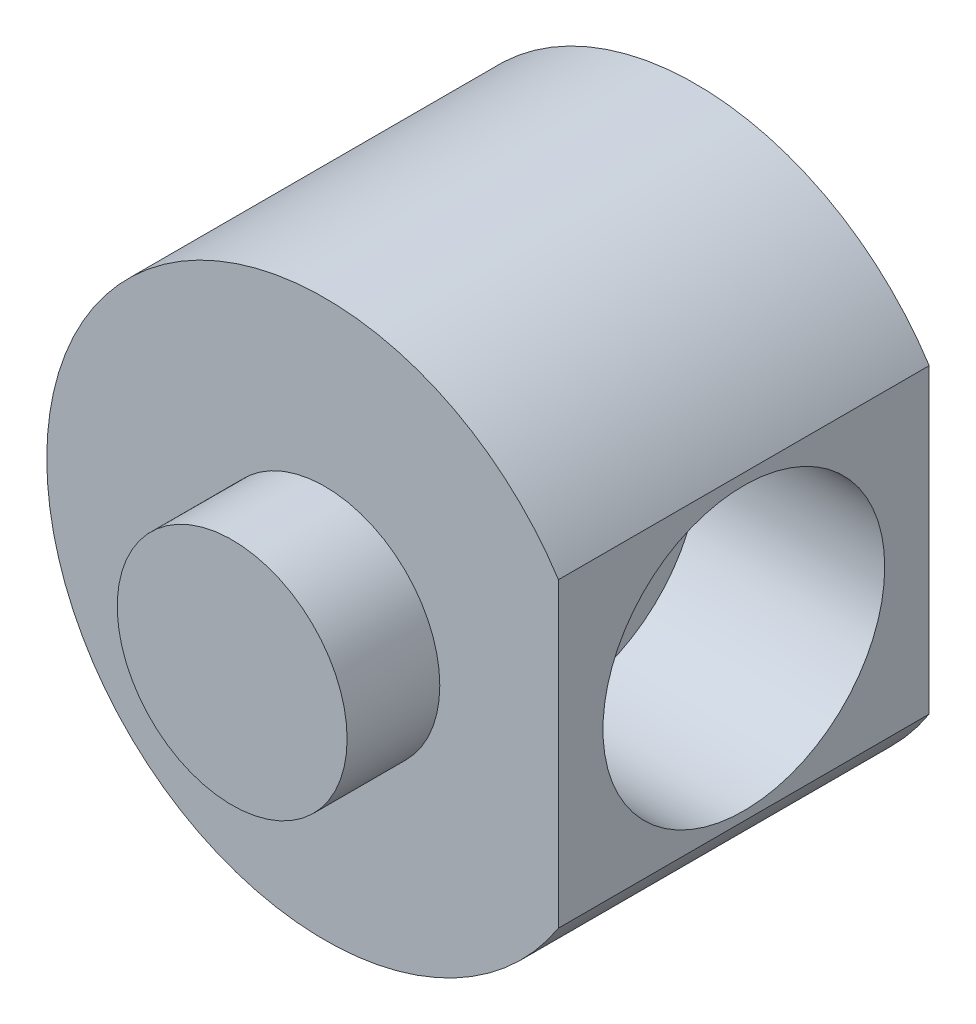
SolidWorks part; units mm, degrees
ref_plane "Front Plane" through (0, 0, 0) normal (0, 0, 1) x (1, 0, 0)
ref_plane "Top Plane" through (0, 0, 0) normal (0, 1, 0) x (1, 0, 0)
ref_plane "Right Plane" through (0, 0, 0) normal (1, 0, 0) x (0, 0, -1)
sketch "Sketch1" plane through (0, 0, 0) normal (0, 1, 0) x (1, 0, 0)
  line L0 (0, 0) -> (3.937, 0)
  line L1 (3.937, 0) -> (3.937, -3.175)
  line L2 (3.937, -3.175) -> (9.525, -3.175)
  line L3 (9.525, -3.175) -> (9.525, -15.875)
  line L4 (9.525, -15.875) -> (3.937, -15.875)
  line L5 (3.937, -15.875) -> (3.937, -19.05)
  line L6 (3.937, -19.05) -> (0, -19.05)
  line L7 (0, -19.05) -> (0, 0)
  dimension "D1" = 3.937
  dimension "D2" = 9.525
  dimension "D3" = 12.7
  dimension "D4" = 19.05
revolve "Revolve1" add sketch "Sketch1" angle 360 about L7
sketch "Sketch2" plane through (0, 0, 15.875) normal (0, 0, 1) x (1, 0, 0)
  line L0 (8.001, 5.1681) -> (8.001, 0)
  line L1 (0, 0) -> (9.525, 0) construction
  line L2 (8.001, 0) -> (8.001, -5.1681)
  line L3 (0, 0) -> (-9.525, 0) construction
  circle A0 centre (0, 0) radius 9.525 construction
  circle A1 centre (0, 0) radius 9.525
  circle M4 centre (0, 0) radius 9.525
  dimension "D1" = 17.526
extrude "Cut-Extrude1" cut sketch "Sketch2" against normal up to surface (12.7 mm away) contours L0 L2 M4 region at (8.615, 0, 15.875) up to face at (3.937, 0, 3.175)
sketch "Sketch3" plane through (8.001, 0, 0) normal (1, 0, 0) x (0, 0, -1)
  line L0 (-3.175, 5.1681) -> (-3.175, -5.1681) construction
  line L5 (-15.875, 5.1681) -> (-3.175, 5.1681)
  line L6 (-15.875, 5.1681) -> (-15.875, -5.1681)
  line L7 (-15.875, -5.1681) -> (-3.175, -5.1681)
  line L8 (-3.175, 5.1681) -> (-3.175, -5.1681)
  circle A0 centre (-9.525, -0.0389) radius 4.826
  circle A1 centre (-9.525, -0.0389) radius 3.175
  dimension "D1" = 6.35
  dimension "D4" = 9.652
  dimension "D5" = 6.35
  dimension "D2" = 5.207
  dimension "D3" = 10.3363
extrude "Cut-Extrude2" cut sketch "Sketch3" against normal through all contours A1 region at (8.001, -0.0389, 9.525)
extrude "Cut-Extrude3" cut sketch "Sketch3<3>" against normal blind 6.35 contours A0 A1 region at (8.001, -0.0389, 14.2145)
sketch "Sketch3<3>" plane through (8.001, 0, 0) normal (1, 0, 0) x (0, 0, -1) same geometry as "Sketch3"
